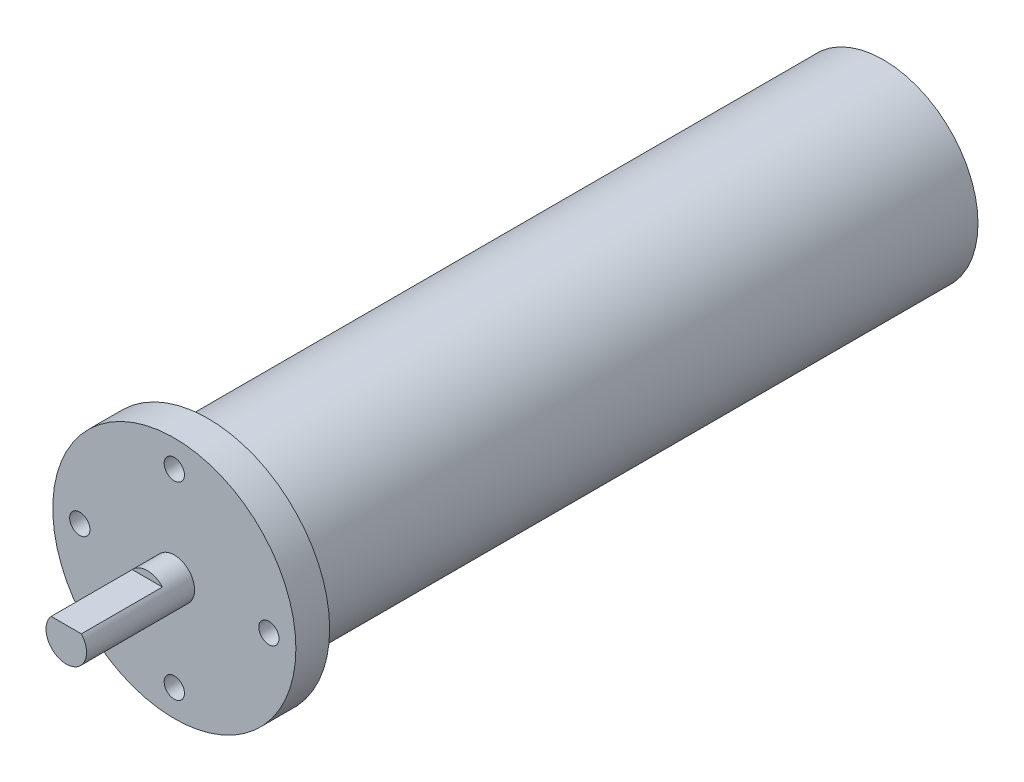
SolidWorks part; units mm, degrees
ref_plane "Front Plane" through (0, 0, 0) normal (0, 0, 1) x (1, 0, 0)
ref_plane "Top Plane" through (0, 0, 0) normal (0, 1, 0) x (1, 0, 0)
ref_plane "Right Plane" through (0, 0, 0) normal (1, 0, 0) x (0, 0, -1)
sketch "Sketch1" plane through (0, 0, 0) normal (0, 0, 1) x (1, 0, 0)
  circle A0 centre (0, 0) radius 14
  dimension "D1" = 28
extrude "Boss-Extrude3" add sketch "Sketch1" along normal blind 100 contours A0
sketch "Sketch4" plane through (0, 0, 100) normal (0, 0, 1) x (1, 0, 0)
  circle A0 centre (0, 0) radius 18
  dimension "D1" = 36
extrude "Boss-Extrude4" add sketch "Sketch4" along normal blind 5
sketch "Sketch5" plane through (0, 0, 105) normal (0, 0, 1) x (1, 0, 0)
  circle A0 centre (0, 0) radius 14 construction
  circle A1 centre (0, 14) radius 1.5
  circle A2 centre (14, 0) radius 1.5
  circle A3 centre (0, -14) radius 1.5
  circle A4 centre (-14, 0) radius 1.5
  dimension "D1" = 28
  dimension "D2" = 3
extrude "Cut-Extrude2" cut sketch "Sketch5" against normal blind 4
sketch "Sketch7" plane through (0, 0, 105) normal (0, 0, 1) x (1, 0, 0)
  circle A0 centre (0, 0) radius 3
  dimension "D1" = 6
extrude "Boss-Extrude7" add sketch "Sketch7" along normal blind 16
sketch "Sketch8" plane through (0, 0, 0) normal (1, 0, 0) x (0, 0, -1)
  line L0 (-121, 3) -> (-121, -3) construction
  line L1 (-124.782, 9.151) -> (-109, 9.151)
  line L2 (-124.782, 9.151) -> (-124.782, 2)
  line L3 (-124.782, 2) -> (-109, 2)
  line L4 (-109, 9.151) -> (-109, 2)
  line L6 (19.8, 0) -> (-19.8, 0) construction
  dimension "D1" = 12
  dimension "D2" = 2
extrude "Cut-Extrude3" cut sketch "Sketch8" against normal mid plane 16
